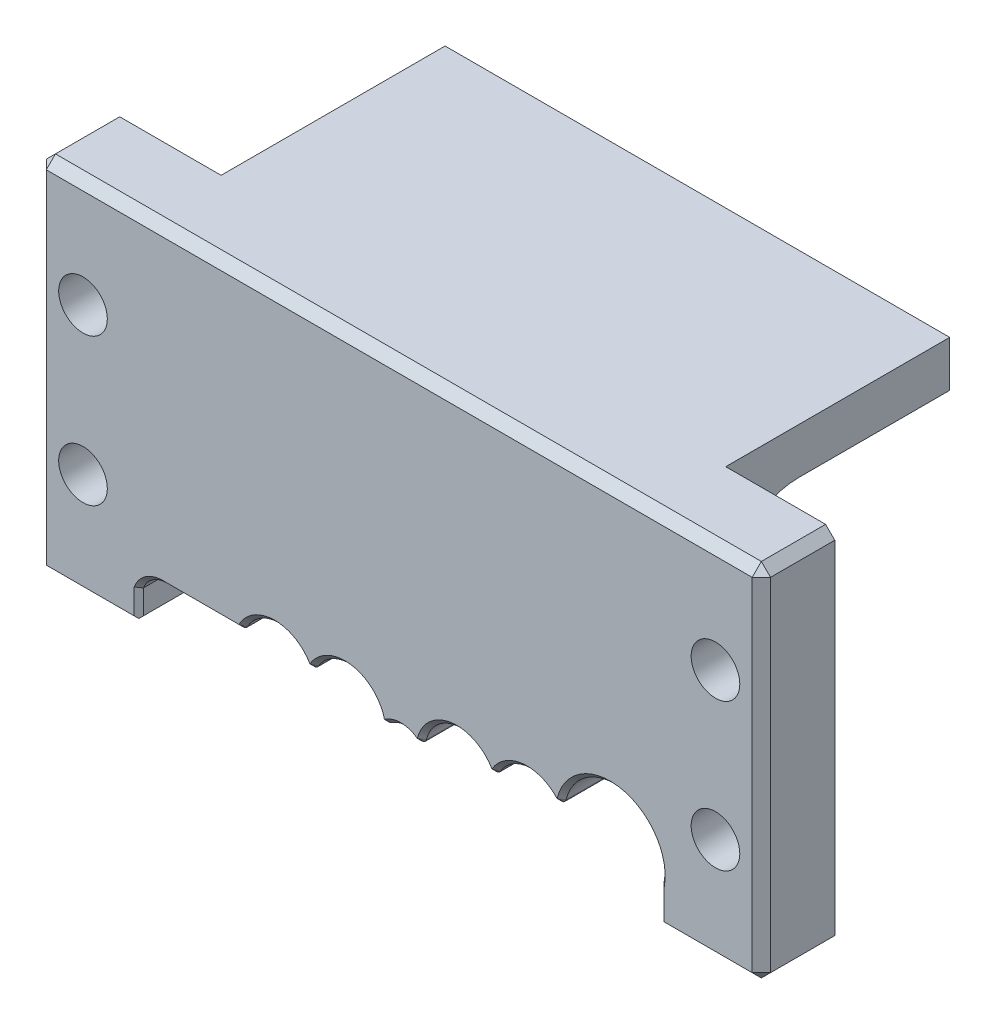
SolidWorks part; units mm, degrees
ref_plane "Front Plane" through (0, 0, 0) normal (0, 0, 1) x (1, 0, 0)
ref_plane "Top Plane" through (0, 0, 0) normal (0, 1, 0) x (1, 0, 0)
ref_plane "Right Plane" through (0, 0, 0) normal (1, 0, 0) x (0, 0, -1)
sketch "Sketch1" plane through (0, 0, 0) normal (0, 1, 0) x (1, 0, 0)
  point P0 (0, 0)
  line B0 (28.37, 45.6802) -> (28.37, 0) construction
  line B1 (28.37, 0) -> (39.45, 0) construction
  line B2 (39.45, 0) -> (39.45, 39.05) construction
  line B3 (39.45, 39.05) -> (36.7, 40.8) construction
  line B4 (36.7, 40.8) -> (36.7, 59.75) construction
  line B5 (36.7, 59.75) -> (32.77, 59.75) construction
  line B6 (32.77, 59.75) -> (32.77, 45.6802) construction
  line B7 (32.77, 45.6802) -> (28.37, 45.6802) construction
  line B8 (-28.37, 0) -> (-28.37, 45.6802) construction
  line B9 (-28.37, 45.6802) -> (-32.77, 45.6802) construction
  line B10 (-32.77, 45.6802) -> (-32.77, 59.75) construction
  line B11 (-32.77, 59.75) -> (-36.7, 59.75) construction
  line B12 (-36.7, 59.75) -> (-36.7, 40.8) construction
  line B13 (-36.7, 40.8) -> (-39.45, 39.05) construction
  line B14 (-39.45, 39.05) -> (-39.45, 0) construction
  line B15 (-39.45, 0) -> (-28.37, 0) construction
  line B16 (28.37, 0) -> (-28.37, 0) construction
  circle B17 centre (34.45, 9.5) radius 2.95 construction
  circle B18 centre (34.45, 25.5) radius 2.95 construction
  circle B19 centre (-34.45, 9.5) radius 2.95 construction
  circle B20 centre (-34.45, 25.5) radius 2.95 construction
sketch_block_instance "Block1-1"
sketch_block "Block1"
sketch "Sketch2" plane through (0, 0, 0) normal (0, 0, 1) x (1, 0, 0)
  line B0 (-39.5328, 0) -> (-39.5328, -39.5) construction
  line B1 (-39.5328, -39.5) -> (-28.4528, -39.5) construction
  line B2 (-28.4528, -39.5) -> (-28.4528, 0) construction
  line B3 (-28.4528, 0) -> (-39.5328, 0) construction
  line B4 (39.3672, -39.5) -> (39.3672, 0) construction
  line B5 (39.3672, 0) -> (28.2872, 0) construction
  line B6 (28.2872, 0) -> (28.2872, -39.5) construction
  line B7 (28.2872, -39.5) -> (39.3672, -39.5) construction
  circle B8 centre (-34.5328, -11.75) radius 2.95 construction
  circle B9 centre (34.3672, -11.75) radius 2.95 construction
  circle B10 centre (-34.5328, -27.75) radius 2.95 construction
  circle B11 centre (34.3672, -27.75) radius 2.95 construction
sketch_block_instance "Block2-1"
sketch_block "Block2"
ref_plane "Plane1" through (0, -39.5, 0) normal (0, 1, 0) x (1, 0, 0)
sketch "Sketch3" plane through (0, 0, 0) normal (0, 1, 0) x (1, 0, 0)
  line L0 (-39.45, 0) -> (-39.45, 32)
  line L1 (-39.45, 39.05) -> (-39.45, 0) construction
  line L2 (-39.45, 32) -> (39.45, 32)
  line L3 (39.45, 0) -> (39.45, 39.05) construction
  line L4 (39.45, 32) -> (39.45, 0)
  line L5 (39.45, 0) -> (-39.45, 0)
  circle A0 centre (-34.45, 9.5) radius 2.375
  circle A1 centre (34.45, 9.5) radius 2.375
  circle A2 centre (-34.45, 25.5) radius 2.375
  circle A3 centre (34.45, 25.5) radius 2.375
  dimension "D2" = 4.75
  dimension "D1" = 32
sketch "Sketch4" plane through (0, 0, 0) normal (0, 0, 1) x (1, 0, 0)
  line L0 (-39.5328, -39.5) -> (-28.4528, -39.5) construction
  line L1 (-39.5328, 0) -> (-39.5328, -39.5) construction
  line L2 (39.3672, -39.5) -> (39.3672, 0) construction
  line L3 (-39.5328, -39.3) -> (-39.5328, 0)
  line L4 (-39.5328, 0) -> (39.3672, 0)
  line L6 (39.3672, 0) -> (39.3672, -39.3)
  line L7 (-39.5328, -39.3) -> (39.3672, -39.3)
  point P10 (-39.5328, 0)
  dimension "D3" = 0.2
extrude "Boss-Extrude2" add sketch "Sketch4" along normal blind 8
sketch "Sketch6" plane through (0, 0, 8) normal (0, 0, 1) x (1, 0, 0)
  line L0 (28.2872, 0) -> (28.2872, -39.5) construction
  line L1 (-28.4528, -39.5) -> (-28.4528, 0) construction
  line L2 (28.2872, -39.5) -> (28.2872, -34.9666)
  line L3 (-25.8528, -33.9) -> (-17.5469, -33.9)
  line L4 (28.2872, -39.5) -> (-28.4528, -39.5)
  line L6 (-28.4528, -39.5) -> (-28.4528, -35.6608)
  line L7 (-39.5328, -39.3) -> (39.3672, -39.3) construction
  line L11 (-39.5328, -39.3) -> (39.3672, -39.3) construction
  circle A0 centre (-25.8528, -36.7) radius 2.6 construction
  circle A1 centre (-13.6386, -35.475) radius 3.825 construction
  circle A2 centre (-5.9886, -35.475) radius 3.825 construction
  circle A3 centre (0.1026, -36.875) radius 2.425 construction
  circle A4 centre (6.1938, -35.475) radius 3.825 construction
  circle A5 centre (13.8438, -35.475) radius 3.825 construction
  circle A6 centre (22.9122, -33.925) radius 5.375 construction
  arc A8 (-10.2458, -33.5015) -> (-17.1053, -33.6345) centre (-13.6386, -35.475) ccw
  arc A9 (-2.1733, -34.5537) -> (-9.3814, -33.5015) centre (-5.9886, -35.475) ccw
  arc A10 (1.5966, -34.8394) -> (-1.3914, -34.8394) centre (0.1026, -36.875) ccw
  arc A11 (9.5866, -33.5015) -> (2.3784, -34.5537) centre (6.1938, -35.475) ccw
  arc A12 (16.7425, -32.8287) -> (10.451, -33.5015) centre (13.8438, -35.475) ccw
  arc A13 (28.2872, -34.9666) -> (17.5971, -32.6115) centre (22.9122, -33.925) ccw
  circle A15 centre (-13.6386, -35.475) radius 3.925 construction
  circle A16 centre (-5.9886, -35.475) radius 3.925 construction
  circle A17 centre (0.1026, -36.875) radius 2.525 construction
  circle A18 centre (6.1938, -35.475) radius 3.925 construction
  circle A19 centre (13.8438, -35.475) radius 3.925 construction
  circle A20 centre (22.9122, -33.925) radius 5.475 construction
  arc A22 (-10.2458, -33.5015) -> (-9.3814, -33.5015) centre (-9.8136, -33.2501) ccw
  arc A23 (-2.1733, -34.5537) -> (-1.3914, -34.8394) centre (-1.6872, -34.4363) ccw
  arc A24 (1.5966, -34.8394) -> (2.3784, -34.5537) centre (1.8924, -34.4363) ccw
  arc A25 (9.5866, -33.5015) -> (10.451, -33.5015) centre (10.0188, -33.2501) ccw
  arc A26 (16.7425, -32.8287) -> (17.5971, -32.6115) centre (17.1117, -32.4916) ccw
  circle A29 centre (-20.6528, -36.7) radius 2.6 construction
  arc A33 (-17.5469, -33.9) -> (-17.1053, -33.6345) centre (-17.5469, -33.4) ccw
  arc A34 (-25.8528, -33.9) -> (-28.4528, -35.6608) centre (-25.8528, -36.7) ccw
  point P14 (-20.6528, -34.1)
  point P19 (-28.4528, -39.5)
  point P24 (-28.4528, -34.5537)
  point P35 (-13.7753, -35.475)
  point P36 (6.7908, -35.475)
  point P37 (27.9044, -36.1731)
  dimension "D1" = 10.75
  dimension "D2" = 7.65
  dimension "D3" = 7.65
  dimension "D4" = 4.85
  dimension "D5" = 7.65
  dimension "D6" = 7.65
  dimension "D7" = 5.2
  dimension "D8" = 0.2
  dimension "D9" = 0.5
  dimension "D11" = 0.1
  dimension "D12" = 0.5
extrude "Cut-Extrude2" cut sketch "Sketch6" against normal up to next
sketch "Sketch7" plane through (0, 0, 8) normal (0, 0, 1) x (1, 0, 0)
  circle A0 centre (-34.5328, -11.75) radius 2.65
  circle A1 centre (-34.5328, -27.75) radius 2.65
  circle A2 centre (34.3672, -11.75) radius 2.65
  circle A3 centre (34.3672, -27.75) radius 2.65
  dimension "D1" = 5.3
extrude "Cut-Extrude3" cut sketch "Sketch7" against normal up to next
chamfer "Chamfer3" distance 1 angle 45 11 edges at (28.2872, -39.3, 4) (33.8272, -39.3, 8) (-28.4528, -39.3, 4) (-33.9928, -39.3, 8) (-39.5328, -39.3, 4) (39.3672, -39.3, 4) (39.3672, 0, 4) (-39.5328, 0, 4) (39.3672, -19.65, 8) (-0.0828, 0, 8) (-39.5328, -19.65, 8)
chamfer "Chamfer4" distance 0.5 angle 45 32 edges at (28.2872, -36.6333, 0) (24.0902, -28.5782, 0) (17.2349, -32.9762, 0) (13.4264, -31.5723, 0) (10.0188, -33.7501, 0) (5.6268, -31.5912, 0) (2.064, -34.9059, 0) (0.1026, -34.35, 0) (-1.8589, -34.9059, 0) (-5.4217, -31.5912, 0) (-9.8136, -33.7501, 0) (-13.7147, -31.5507, 0) (-17.2893, -33.8285, 0) (-21.6998, -33.9, 0) (-27.4228, -34.3816, 0) (-28.4528, -36.9804, 0) (28.2872, -36.6333, 8) (24.0902, -28.5782, 8) (17.2349, -32.9762, 8) (13.4264, -31.5723, 8) (10.0188, -33.7501, 8) (5.6268, -31.5912, 8) (2.064, -34.9059, 8) (0.1026, -34.35, 8) (-1.8589, -34.9059, 8) (-5.4217, -31.5912, 8) (-9.8136, -33.7501, 8) (-13.7147, -31.5507, 8) (-17.2893, -33.8285, 8) (-21.6998, -33.9, 8) (-27.4228, -34.3816, 8) (-28.4528, -36.9804, 8)
sketch "Sketch8" plane through (0, 0, 0) normal (0, 0, -1) x (-1, 0, 0)
  line L0 (-38.3672, 0) -> (38.5328, 0) construction
  line L1 (-27.4872, 0) -> (27.4872, 0)
  line L2 (-27.4872, 0) -> (-27.4872, -5)
  line L3 (-27.4872, -5) -> (27.4872, -5)
  line L4 (27.4872, 0) -> (27.4872, -5)
  line L5 (0, -5) -> (0, 0) construction
  line L6 (-27.4872, -2.5) -> (27.4872, -2.5) construction
  line L7 (-28.2872, 0) -> (-28.2872, -39.5) construction
  point P172 (0, -2.5)
  dimension "D1" = 0.8
  dimension "D2" = 5
extrude "Boss-Extrude3" add sketch "Sketch8" along normal blind 24.4
fillet "Fillet1" radius 8 1 edges at (0, -5, 0)
